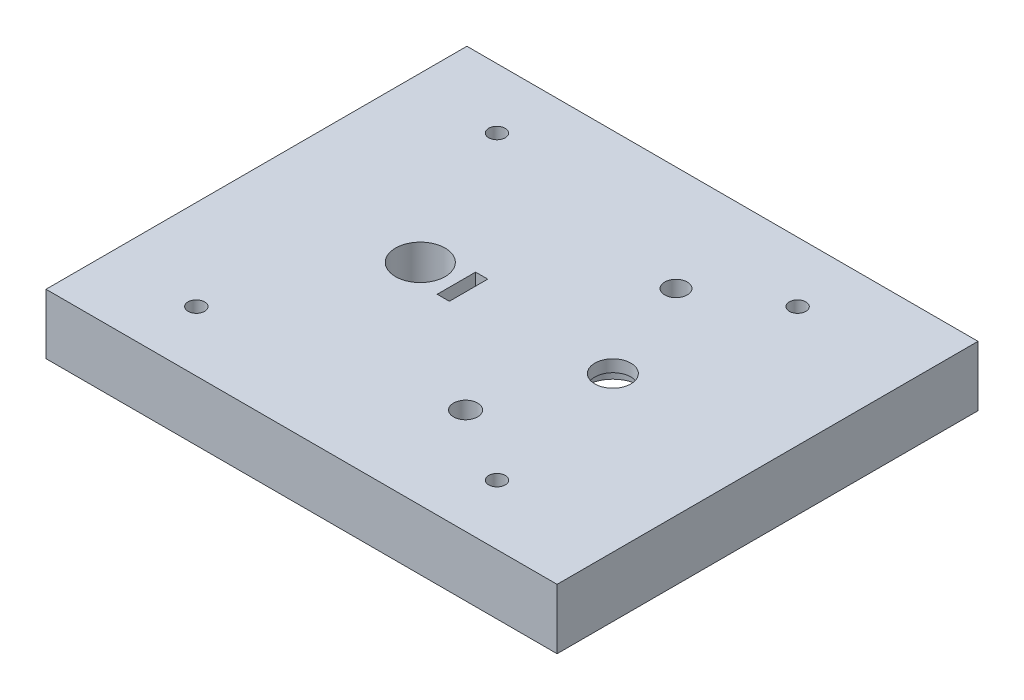
SolidWorks part; units mm, degrees
ref_plane "Front Plane" through (0, 0, 0) normal (0, 0, 1) x (1, 0, 0)
ref_plane "Top Plane" through (0, 0, 0) normal (0, 1, 0) x (1, 0, 0)
ref_plane "Right Plane" through (0, 0, 0) normal (1, 0, 0) x (0, 0, -1)
sketch "Sketch1" plane through (0, 0, 0) normal (0, 1, 0) x (1, 0, 0)
  line L1 (-52.2759, 35) -> (32.7241, 35)
  line L2 (-52.2759, 35) -> (-52.2759, -35)
  line L3 (-52.2759, -35) -> (32.7241, -35)
  line L4 (32.7241, 35) -> (32.7241, -35)
  line L11 (5.5, 2.0001) -> (5.5, -1.9999)
  line L13 (8.5, 2.0001) -> (8.5, -1.9999)
  line L16 (3.625, 17.5) -> (3.625, 13.7295)
  line L17 (-3.625, 17.5) -> (-3.625, 13.7295)
  line L18 (3.625, -17.5) -> (3.625, -13.7295)
  line L19 (-3.625, -17.5) -> (-3.625, -13.7295)
  line L20 (-17, -7) -> (-17, 7)
  line L21 (-17, -7) -> (-12.3548, -7)
  line L22 (-17, 7) -> (-12.3548, 7)
  line L24 (-19.0247, -3.193) -> (-19.0247, 3.193)
  line L25 (-19.0247, 3.193) -> (-17, 3.193)
  line L33 (-19.0247, -3.193) -> (-17, -3.193)
  circle A0 centre (-37.2759, 25) radius 1.375
  circle A1 centre (12.7241, 25) radius 1.375
  circle A2 centre (12.7241, -25) radius 1.375
  circle A3 centre (-37.2759, -25) radius 1.375
  arc A6 (5.5, 2.0001) -> (8.5, 2.0001) centre (7, 0) cw
  arc A7 (5.5, -1.9999) -> (8.5, -1.9999) centre (7, 0) ccw
  circle A8 centre (7, 0) radius 4.5
  circle A12 centre (-25.0247, 0) radius 4.125
  circle A13 centre (7, 0) radius 3
  arc A14 (-3.625, 13.7295) -> (-12.3548, 7) centre (0, 0) ccw
  circle A17 centre (85.0307, -10.8481) radius 14
  circle A18 centre (86.1334, -28.3481) radius 2
  circle A19 centre (86.1334, 6.6519) radius 2
  arc A20 (-3.625, 13.7295) -> (-12.3548, 7) centre (0, 0) ccw
  circle A21 centre (0, 17.5) radius 1.875
  circle A22 centre (0, -17.5) radius 2
  arc A23 (3.625, 17.5) -> (-3.625, 17.5) centre (0, 17.5) ccw
  arc A24 (-3.625, -17.5) -> (3.625, -17.5) centre (0, -17.5) ccw
  arc A26 (3.625, -13.7295) -> (3.625, 13.7295) centre (0, 0) ccw
  arc A27 (3.625, -13.7295) -> (3.625, 13.7295) centre (0, 0) ccw
  arc A28 (-12.3548, -7) -> (-3.625, -13.7295) centre (0, 0) ccw
  arc A29 (-12.3548, -7) -> (-3.625, -13.7295) centre (0, 0) ccw
  point P0 (0, 0)
  point P11 (-19.0247, 0)
  point P20 (-17, 0)
  point P68 (3.625, 15.6148)
  dimension "D3" = 15
  dimension "D6" = 2.75
  dimension "D7" = 17
  dimension "D10" = 4.6452
  dimension "D11" = 9
  dimension "D12" = 35
  dimension "D13" = 3.75
  dimension "D14" = 6.386
  dimension "D15" = 1.1027
  dimension "D17" = 1.1027
  dimension "D20" = 8.25
  dimension "D21" = 6
  dimension "D16" = 14
  dimension "D25" = 14.2
  dimension "D1" = 85
  dimension "D2" = 70
  dimension "D4" = 10
  dimension "D8" = 4
  dimension "D9" = 3
  dimension "D18" = 2.0247
  dimension "D19" = 4
  dimension "D22" = 32.7241
  dimension "D23" = 6
  dimension "D24" = 7
  dimension "D26" = 35
  dimension "D27" = 17.5
  dimension "D28" = 50
  dimension "D29" = 50
  dimension "D31" = 7.25
  dimension "D32" = 7.25
  dimension "D5" = 2
extrude "Boss-Extrude4" add sketch "Sketch1" along normal blind 10 contours L4 L1 L2 L3 A14 A2 A1 A0 A3 | A14 | A14 | A14 | A14 | A14 A8 | A8 A13 | A14 | L16 A23 L17 A14 A20 A21 | L19 A24 L18 A14 A22 region at (-9.7759, 0, -33.8989) region at (-1.7092, 0, -0.0389) region at (2.6273, 0, 0)
extrude "Cut-Extrude2" cut sketch "Sketch1<7>" along normal blind 6 contours L24 L33 L20 L25 | L21 A28 L19 A24 L18 A26 L16 A23 L17 A14 L22 L20 A8 A21 A22 region at (-1.7092, 0, -0.0389) region at (-18.0123, 0, 0)
sketch "Sketch1<7>" plane through (0, 0, 0) normal (0, 1, 0) x (1, 0, 0) same geometry as "Sketch1"
extrude "Cut-Extrude10" cut sketch "Sketch1<11>" along normal blind 8 contours A8 A13 region at (2.6273, 0, 0)
sketch "Sketch1<11>" plane through (0, 0, 0) normal (0, 1, 0) x (1, 0, 0) same geometry as "Sketch1"
